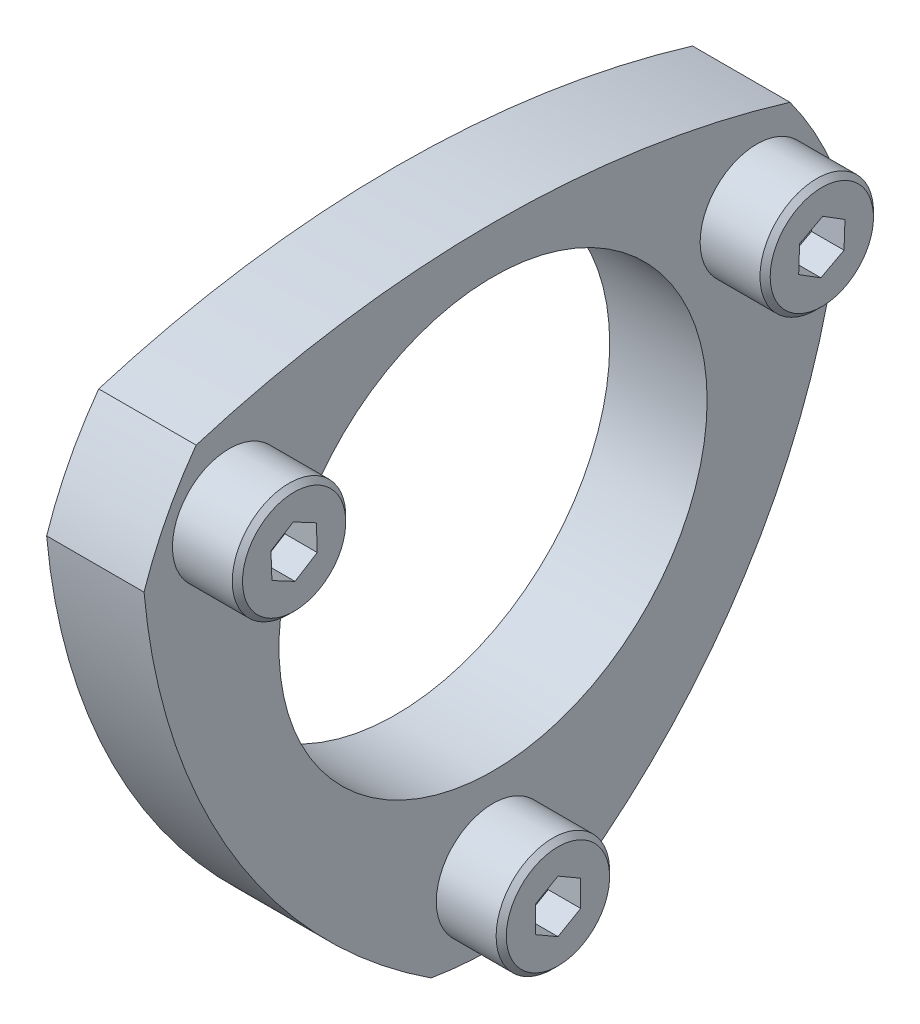
SolidWorks part; units mm, degrees
material "Plain Carbon Steel"
ref_plane "Front Plane" through (0, 0, 0) normal (0, 0, 1) x (1, 0, 0)
ref_plane "Top Plane" through (0, 0, 0) normal (0, 1, 0) x (1, 0, 0)
ref_plane "Right Plane" through (0, 0, 0) normal (1, 0, 0) x (0, 0, -1)
sketch "Sketch1" plane through (0, 0, 0) normal (1, 0, 0) x (0, 0, -1)
  arc A0 (-17.3395, 5.7329) -> (-3.0786, -18.0012) centre (14.2825, 8.5818) ccw
  arc A1 (-3.0786, -18.0012) -> (3.0786, -18.0012) centre (0, 0) ccw
  arc A2 (3.0786, -18.0012) -> (17.3395, 5.7329) centre (-14.2825, 8.5818) ccw
  arc A3 (17.3395, 5.7329) -> (14.7528, 10.7646) centre (0, 0) ccw
  arc A4 (14.7528, 10.7646) -> (-14.7528, 10.7646) centre (0, -37.846) ccw
  arc A5 (-14.7528, 10.7646) -> (-17.3395, 5.7329) centre (0, 0) ccw
  circle A6 centre (0, 0) radius 10.6362
extrude "Boss-Extrude1" add sketch "Sketch1" along normal blind 4.8387
ref_plane "Plane1" through (0, 0, 0) normal (0, -0.8829, 0.4695) x (-1, 0, 0)
hole_wizard "Hole1" positions "Sketch3" profile "Sketch2" legacy
sketch "Sketch3" plane through (4.8387, 0, 0) normal (1, 0, 0) x (0, 0, -1)
  point P0 (-13.1085, 6.9699)
sketch "Sketch2" plane through (4.8387, 6.9699, 13.1085) normal (0, 1, 0) x (0, 0, -1)
  line L0 (0, 0) -> (0, 4.8387)
  line L1 (0, 4.8387) -> (1.8796, 4.8387)
  line L2 (1.8796, 4.8387) -> (1.8796, 0)
  line L3 (1.8796, 0) -> (0, 0)
  line L4 (0, 110) -> (0, -10) construction
  dimension "Diameter" = 3.7592
  dimension "Depth" = 4.8387
sketch "Sketch4" plane through (0, 0, 0) normal (0, -0.8829, 0.4695) x (-1, 0, 0)
  line L0 (-4.8387, -14.8463) -> (-4.8387, -17.6657)
  line L1 (-4.8387, -17.6657) -> (-7.8105, -17.6657)
  line L2 (-7.8105, -17.6657) -> (-8.0645, -17.4117)
  line L3 (-8.0645, -17.4117) -> (-8.0645, -14.8463)
  line L4 (-8.0645, -14.8463) -> (-4.8387, -14.8463)
  line L5 (-8.0645, -14.8463) -> (-4.8387, -14.8463) construction
revolve "Revolve1" add sketch "Sketch4" angle 360 about L5 reverse direction yes
ref_plane "Plane2" through (0, 0, 0) normal (0, 0.8829, 0.4695) x (1, 0, 0)
hole_wizard "Hole2" positions "Sketch6" profile "Sketch5" legacy
sketch "Sketch6" plane through (4.8387, 0, 0) normal (1, 0, 0) x (0, 0, -1)
  point P0 (13.1085, 6.9699)
sketch "Sketch5" plane through (4.8387, 6.9699, -13.1085) normal (0, 1, 0) x (0, 0, -1)
  line L0 (0, 0) -> (0, 4.8387)
  line L1 (0, 4.8387) -> (1.8796, 4.8387)
  line L2 (1.8796, 4.8387) -> (1.8796, 0)
  line L3 (1.8796, 0) -> (0, 0)
  line L4 (0, 110) -> (0, -10) construction
  dimension "Diameter" = 3.7592
  dimension "Depth" = 4.8387
sketch "Sketch7" plane through (0, 0, 0) normal (0, 0.8829, 0.4695) x (1, 0, 0)
  line L0 (4.8387, 14.8463) -> (4.8387, 17.6657)
  line L1 (4.8387, 17.6657) -> (7.8105, 17.6657)
  line L2 (7.8105, 17.6657) -> (8.0645, 17.4117)
  line L3 (8.0645, 17.4117) -> (8.0645, 14.8463)
  line L4 (8.0645, 14.8463) -> (4.8387, 14.8463)
  line L5 (8.0645, 14.8463) -> (4.8387, 14.8463) construction
revolve "Revolve2" add sketch "Sketch7" angle 360 about L5 reverse direction yes
hole_wizard "Hole3" positions "Sketch9" profile "Sketch8" legacy
sketch "Sketch9" plane through (4.8387, 0, 0) normal (1, 0, 0) x (0, 0, -1)
  point P0 (0, -14.8463)
sketch "Sketch8" plane through (4.8387, -14.8463, 0) normal (0, 1, 0) x (0, 0, -1)
  line L0 (0, 0) -> (0, 4.8387)
  line L1 (0, 4.8387) -> (1.8796, 4.8387)
  line L2 (1.8796, 4.8387) -> (1.8796, 0)
  line L3 (1.8796, 0) -> (0, 0)
  line L4 (0, 110) -> (0, -10) construction
  dimension "Diameter" = 3.7592
  dimension "Depth" = 4.8387
sketch "Sketch10" plane through (0, 0, 0) normal (0, 0, 1) x (1, 0, 0)
  line L0 (4.8387, -14.8463) -> (4.8387, -12.0269)
  line L1 (4.8387, -12.0269) -> (7.8105, -12.0269)
  line L2 (7.8105, -12.0269) -> (8.0645, -12.2809)
  line L3 (8.0645, -12.2809) -> (8.0645, -14.8463)
  line L4 (8.0645, -14.8463) -> (4.8387, -14.8463)
  line L5 (8.0645, -14.8463) -> (4.8387, -14.8463) construction
revolve "Revolve3" add sketch "Sketch10" angle 360 about L5 reverse direction yes
ref_plane "Plane3" through (0, 0, 0) normal (0, 0.8829, 0.4695) x (1, 0, 0)
ref_plane "Plane4" through (0, 0, 0) normal (0, -0.8829, 0.4695) x (-1, 0, 0)
ref_plane "Plane5" through (8.0645, 0, 0) normal (1, 0, 0) x (0, 0, -1)
sketch "Sketch11" plane through (8.0645, 0, 0) normal (1, 0, 0) x (0, 0, -1)
  line L0 (-1.1278, -14.1952) -> (-1.1278, -15.4974)
  line L1 (-1.1278, -15.4974) -> (0, -16.1485)
  line L2 (0, -16.1485) -> (1.1278, -15.4974)
  line L3 (1.1278, -15.4974) -> (1.1278, -14.1952)
  line L4 (1.1278, -14.1952) -> (0, -13.5441)
  line L5 (0, -13.5441) -> (-1.1278, -14.1952)
extrude "Cut-Extrude1" cut sketch "Sketch11" against normal blind 1.6129
sketch "Sketch12" plane through (8.0645, 0, 0) normal (1, 0, 0) x (0, 0, -1)
  line L0 (11.9587, 6.3586) -> (13.0631, 5.6685)
  line L1 (13.0631, 5.6685) -> (14.2129, 6.2798)
  line L2 (14.2129, 6.2798) -> (14.2583, 7.5813)
  line L3 (14.2583, 7.5813) -> (13.154, 8.2713)
  line L4 (13.154, 8.2713) -> (12.0042, 7.66)
  line L5 (12.0042, 7.66) -> (11.9587, 6.3586)
extrude "Cut-Extrude2" cut sketch "Sketch12" against normal blind 1.6129
sketch "Sketch13" plane through (8.0645, 0, 0) normal (1, 0, 0) x (0, 0, -1)
  line L0 (-14.2583, 7.5813) -> (-14.2129, 6.2798)
  line L1 (-14.2129, 6.2798) -> (-13.0631, 5.6685)
  line L2 (-13.0631, 5.6685) -> (-11.9587, 6.3586)
  line L3 (-11.9587, 6.3586) -> (-12.0042, 7.66)
  line L4 (-12.0042, 7.66) -> (-13.154, 8.2713)
  line L5 (-13.154, 8.2713) -> (-14.2583, 7.5813)
extrude "Cut-Extrude3" cut sketch "Sketch13" against normal blind 1.6129
ref_plane "rr XY" through (0, 0, 0) normal (1, 0, 0) x (0, 0, -1)
ref_plane "rr XZ" through (0, 0, 0) normal (0, -1, 0) x (-1, 0, 0)
ref_plane "rr YZ" through (0, 0, 0) normal (0, 0, -1) x (-1, 0, 0)
ref_axis "rr X" through (0, 0, 80.9) along (0, 0, -1)
ref_axis "rr Y" through (0, -50, 0) along (0, 1, 0)
ref_axis "rr Z" through (80.9, 0, 0) along (-1, 0, 0)
sketch3d "rr"
  point P0 (0, 0, 0)
